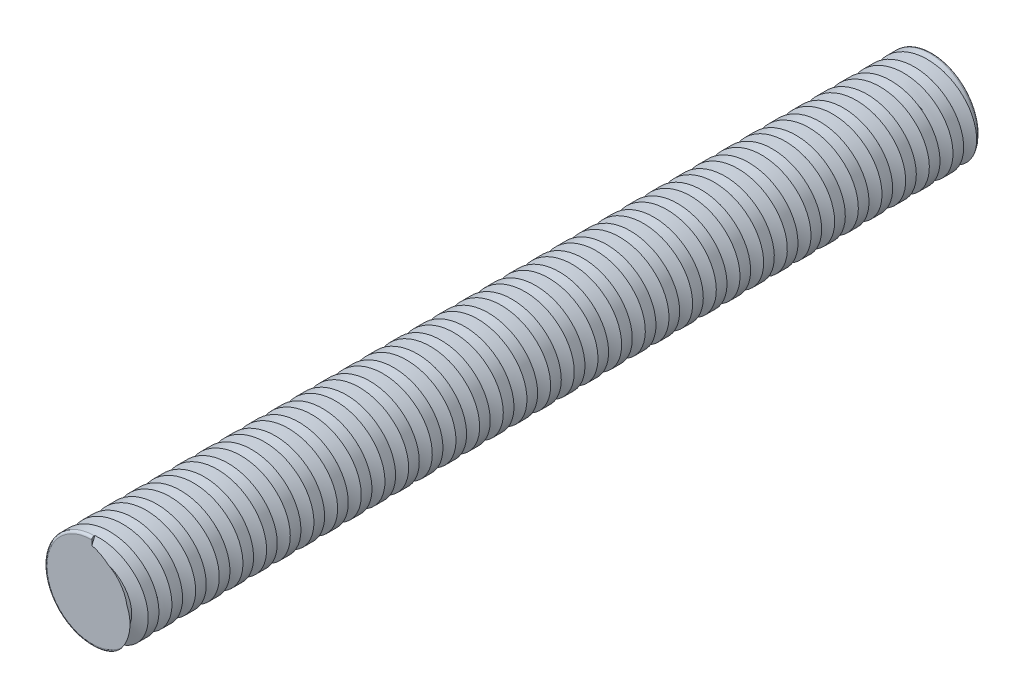
SolidWorks part; units mm, degrees
ref_plane "Front Plane" through (0, 0, 0) normal (0, 0, 1) x (1, 0, 0)
ref_plane "Top Plane" through (0, 0, 0) normal (0, 1, 0) x (1, 0, 0)
ref_plane "Right Plane" through (0, 0, 0) normal (1, 0, 0) x (0, 0, -1)
sketch "Sketch1" plane through (0, 0, 0) normal (0, 0, 1) x (1, 0, 0)
  circle A0 centre (0, 0) radius 4
  dimension "D1" = 8
extrude "Boss-Extrude1" add sketch "Sketch1" against normal blind 71
fillet "Fillet1" radius 0.2 2 edges at (4, 0, -71) (4, 0, 0)
sketch "Sketch2" plane through (0, 0, 0) normal (0, 0, 1) x (1, 0, 0)
  circle A0 centre (0, 0) radius 4
  dimension "D1" = 8
sketch "Sketch3" plane through (0, 0, 0) normal (0, 1, 0) x (1, 0, 0)
  line L0 (3, 0.35) -> (3, 0.05)
  line L1 (3, 0.05) -> (5, -0.75)
  line L2 (5, -0.75) -> (5, 1.15)
  line L3 (5, 1.15) -> (3, 0.35)
  line L4 (5, 0.2) -> (3, 0.2)
  line L7 (4, 0.2) -> (-4, 0.2) construction
  point P7 (4, 0.2)
  dimension "D1" = 1.9
  dimension "D2" = 2
  dimension "D3" = 0.3
  dimension "D4" = 4
curve "Helix/Spiral1" pitch 2 height 71 turns 35.5
sweep "Cut-Sweep1" cut profiles "Sketch3" path "Helix/Spiral1"
